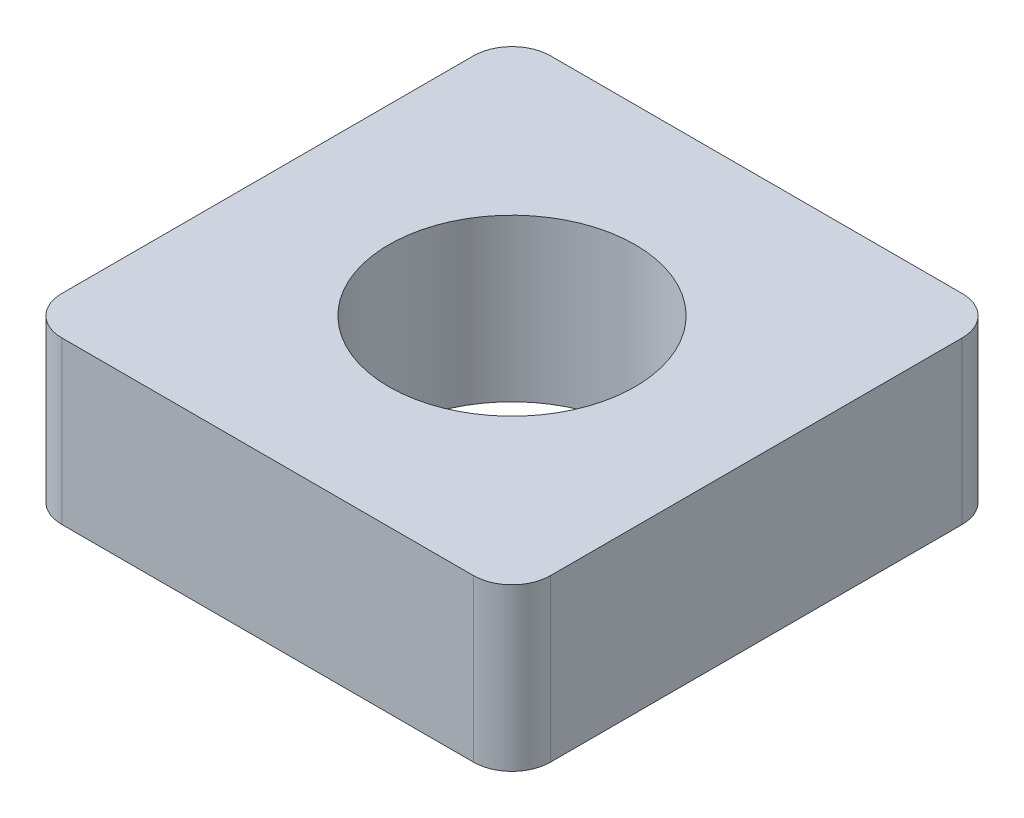
SolidWorks part; units mm, degrees
ref_plane "Front Plane" through (0, 0, 0) normal (0, 0, 1) x (1, 0, 0)
ref_plane "Top Plane" through (0, 0, 0) normal (0, 1, 0) x (1, 0, 0)
ref_plane "Right Plane" through (0, 0, 0) normal (1, 0, 0) x (0, 0, -1)
sketch "Sketch1" plane through (0, 0, 0) normal (0, 1, 0) x (1, 0, 0)
  line L0 (-3.175, 3.175) -> (3.175, -3.175) construction
  line L1 (-2.675, 3.175) -> (2.675, 3.175)
  line L2 (-3.175, 2.675) -> (-3.175, -2.675)
  line L3 (-2.675, -3.175) -> (2.675, -3.175)
  line L4 (3.175, 2.675) -> (3.175, -2.675)
  circle A0 centre (0, 0) radius 1.6
  arc A1 (-2.675, 3.175) -> (-3.175, 2.675) centre (-2.675, 2.675) ccw
  arc A2 (2.675, -3.175) -> (3.175, -2.675) centre (2.675, -2.675) ccw
  arc A3 (2.675, 3.175) -> (3.175, 2.675) centre (2.675, 2.675) cw
  arc A4 (-3.175, -2.675) -> (-2.675, -3.175) centre (-2.675, -2.675) ccw
  point P15 (3.175, 3.175)
  dimension "D2" = 3.2
  dimension "D3" = 0.5
  dimension "D1" = 6.35
extrude "Boss-Extrude1" add sketch "Sketch1" along normal blind 1.05 and the other way blind 1.05
